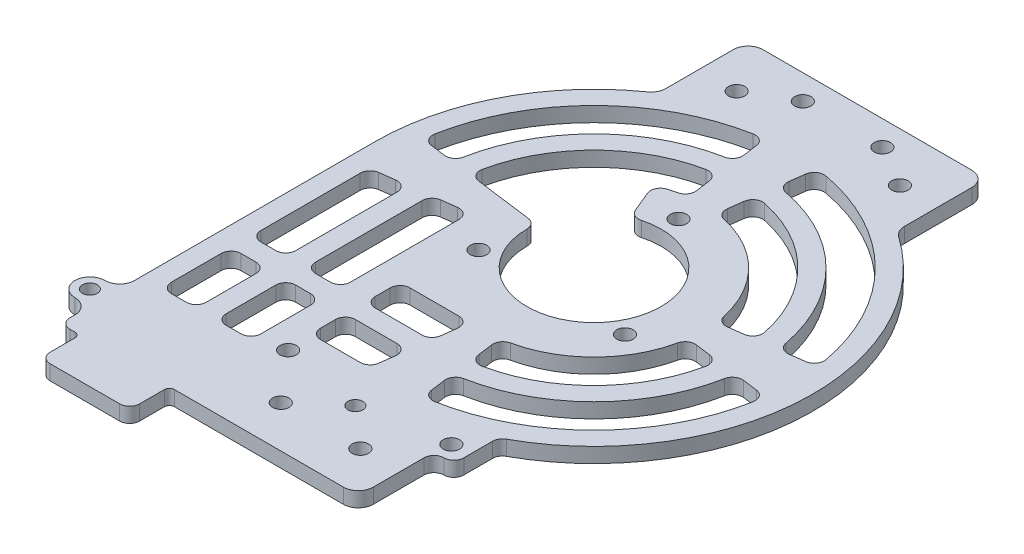
SolidWorks part; units mm, degrees
material "Thornel Mat VMA"
ref_plane "前视基准面" through (0, 0, 0) normal (0, 0, 1) x (1, 0, 0)
ref_plane "上视基准面" through (0, 0, 0) normal (0, 1, 0) x (1, 0, 0)
ref_plane "右视基准面" through (0, 0, 0) normal (1, 0, 0) x (0, 0, -1)
other "Configuration Table"
sketch "草图1" plane through (0, 0, 0) normal (0, 1, 0) x (1, 0, 0)
  line L0 (-44, 0) -> (-44, -52)
  line L1 (-44, -52) -> (16, -52)
  line L2 (-21.8118, 2.8716) -> (-13.3845, 1.7621)
  line L3 (-2.8716, 21.8118) -> (-3.7853, 28.7519)
  line L4 (2.8716, 21.8118) -> (3.7853, 28.7519)
  line L5 (0, 0) -> (0, 69.078) construction
  line L6 (21.8118, -2.8716) -> (28.7519, -3.7853)
  line L7 (21.8118, 2.8716) -> (28.7519, 3.7853)
  line L8 (-2.8716, -21.8118) -> (-3.7853, -28.7519)
  line L9 (2.8716, -21.8118) -> (3.7853, -28.7519)
  line L10 (-21.8118, 2.8716) -> (-28.7519, 3.7853)
  line L11 (-21.8118, -2.8716) -> (-28.7519, -3.7853)
  line L12 (32.7177, 4.3074) -> (39.6578, 5.221)
  line L13 (32.7177, -4.3074) -> (39.6578, -5.221)
  line L14 (-4.3074, 32.7177) -> (-5.221, 39.6578)
  line L15 (4.3074, 32.7177) -> (5.221, 39.6578)
  line L16 (-32.7177, 4.3074) -> (-39.6578, 5.221)
  line L17 (-32.7177, -4.3074) -> (-39.6578, -5.221)
  line L18 (-4.3074, -32.7177) -> (-5.221, -39.6578)
  line L19 (4.3074, -32.7177) -> (5.221, -39.6578)
  line L20 (21.8118, 2.8716) -> (13.3845, 1.7621)
  line L21 (-5.1662, 12.4724) -> (-8.419, 20.3253)
  line L22 (5.1662, 12.4724) -> (8.419, 20.3253)
  arc A0 (44, 0) -> (-44, 0) centre (0, 0) ccw
  circle A1 centre (0, 0) radius 31 construction
  circle A2 centre (0, 0) radius 17 construction
  circle A3 centre (0, 17) radius 1.65
  circle A4 centre (14.7224, -8.5) radius 1.65
  circle A5 centre (-14.7224, -8.5) radius 1.65
  circle A6 centre (0, 0) radius 13.5
  arc A7 (21.8118, 2.8716) -> (2.8716, 21.8118) centre (0, 0) ccw
  arc A8 (28.7519, 3.7853) -> (3.7853, 28.7519) centre (0, 0) ccw
  arc A9 (32.7177, 4.3074) -> (4.3074, 32.7177) centre (0, 0) ccw
  arc A10 (39.6578, 5.221) -> (5.221, 39.6578) centre (0, 0) ccw
  arc A11 (-2.8716, 21.8118) -> (-21.8118, 2.8716) centre (0, 0) ccw
  arc A12 (-3.7853, 28.7519) -> (-28.7519, 3.7853) centre (0, 0) ccw
  arc A13 (-4.3074, 32.7177) -> (-32.7177, 4.3074) centre (0, 0) ccw
  arc A14 (-5.221, 39.6578) -> (-39.6578, 5.221) centre (0, 0) ccw
  arc A15 (-32.7177, -4.3074) -> (-4.3074, -32.7177) centre (0, 0) ccw
  arc A16 (-28.7519, -3.7853) -> (-3.7853, -28.7519) centre (0, 0) ccw
  arc A17 (-39.6578, -5.221) -> (-5.221, -39.6578) centre (0, 0) ccw
  arc A18 (3.7853, -28.7519) -> (28.7519, -3.7853) centre (0, 0) ccw
  arc A19 (4.3074, -32.7177) -> (32.7177, -4.3074) centre (0, 0) ccw
  arc A20 (5.221, -39.6578) -> (39.6578, -5.221) centre (0, 0) ccw
  arc A21 (2.8716, -21.8118) -> (21.8118, -2.8716) centre (0, 0) ccw
  arc A22 (-21.8118, -2.8716) -> (-2.8716, -21.8118) centre (0, 0) ccw
  arc A24 (44, 0) -> (16, -52) centre (-18.2857, 0) cw
  point P17 (0, 0)
  point P40 (0, 0)
  dimension "D1" = 88
  dimension "D2" = 62
  dimension "D3" = 34
  dimension "D4" = 3.3
  dimension "D8" = 27
  dimension "D9" = 44
  dimension "D10" = 58
  dimension "D11" = 66
  dimension "D12" = 80
  dimension "D5" = 52
  dimension "D6" = 60
  dimension "D13" = 15
  dimension "D15" = 22.5
  dimension "D16" = 22.5
  dimension "D7" = 3
  dimension "D14" = 4
extrude "凸台-拉伸1" add sketch "草图1" along normal blind 3 contours A0 A20 L19 A19 L13 A17 L17 A15 L18 A14 L14 A13 L16 A12 L3 A11 L10 A10 L12 A9 L15 A8 L7 A7 L4 A6 A5 A4 A3 L9 A21 L6 A18 L11 A22 L8 A16 | A0 L0 L1 | L20 A7 L22 A6 | L18 A17 L17 A15 | L8 A16 L11 A22 region at (0, 0, -42.6977) region at (13.7043, 0, -10.5157)
sketch "草图2" plane through (0, 3, 0) normal (0, 1, 0) x (1, 0, 0)
  line L0 (-31, 0) -> (-31, -68.0994) construction
  line L1 (-4.0812, -31) -> (-59.0383, -31) construction
  line L2 (-29, -3.8179) -> (-29, -29)
  line L3 (-33, -4.3445) -> (-33, -29)
  line L4 (-40, -5.2661) -> (-40, -29)
  line L5 (-22, -2.8964) -> (-22, -29)
  line L6 (-44, 0) -> (-44, -52) construction
  line L7 (-3.8179, -29) -> (-17, -29)
  line L8 (-4.3445, -33) -> (-17, -33)
  line L9 (-5.2661, -40) -> (-17, -40)
  line L10 (-2.8964, -22) -> (-17, -22)
  line L11 (-22, -2.8964) -> (-29, -3.8179)
  line L12 (-40, -47) -> (-33, -47)
  line L13 (-29, -47) -> (-22, -47)
  line L14 (-44, -52) -> (16, -52) construction
  line L15 (-33, -4.3445) -> (-40, -5.2661)
  line L16 (-17, -22) -> (-17, -29)
  line L19 (-17, -33) -> (-17, -40)
  line L20 (-2.8964, -22) -> (-3.8179, -29)
  line L21 (-4.3445, -33) -> (-5.2661, -40)
  line L22 (-22, -29) -> (-29, -29)
  line L23 (-22, -33) -> (-29, -33)
  line L24 (-40, -33) -> (-40, -47)
  line L25 (-33, -33) -> (-33, -47)
  line L26 (-33, -29) -> (-40, -29)
  line L27 (-33, -33) -> (-40, -33)
  line L28 (-29, -33) -> (-29, -47)
  line L29 (-22, -33) -> (-22, -47)
  dimension "D1" = 31
  dimension "D2" = 31
  dimension "D3" = 2
  dimension "D4" = 2
  dimension "D5" = 4
  dimension "D6" = 22
  dimension "D7" = 97.5
  dimension "D8" = 5
  dimension "D9" = 2
  dimension "D10" = 2
  dimension "D11" = 97.5
  dimension "D12" = 9
  dimension "D13" = 9
  dimension "D14" = 5
extrude "切除-拉伸1" cut sketch "草图2" against normal blind 5
fillet "圆角1" radius 2 50 edges at (5.221, 1.5, 39.6578) (4.3074, 1.5, 32.7177) (32.7177, 1.5, 4.3074) (39.6578, 1.5, 5.221) (-5.221, 1.5, -39.6578) (-4.3074, 1.5, -32.7177) (-32.7177, 1.5, -4.3074) (-39.6578, 1.5, -5.221) (-3.7853, 1.5, -28.7519) (-2.8716, 1.5, -21.8118) (-28.7519, 1.5, -3.7853) (39.6578, 1.5, -5.221) (32.7177, 1.5, -4.3074) (4.3074, 1.5, -32.7177) (5.221, 1.5, -39.6578) (28.7519, 1.5, -3.7853) (21.8118, 1.5, -2.8716) (2.8716, 1.5, -21.8118) (3.7853, 1.5, -28.7519) (2.8716, 1.5, 21.8118) (21.8118, 1.5, 2.8716) (28.7519, 1.5, 3.7853) (3.7853, 1.5, 28.7519) (-17, 1.5, 40) (-17, 1.5, 33) (-4.3445, 1.5, 33) (-5.2661, 1.5, 40) (-29, 1.5, 3.8179) (-22, 1.5, 2.8964) (-2.8964, 1.5, 22) (-3.8179, 1.5, 29) (-17, 1.5, 29) (-17, 1.5, 22) (-33, 1.5, 4.3445) (-40, 1.5, 5.2661) (-22, 1.5, 29) (-29, 1.5, 29) (-40, 1.5, 47) (-40, 1.5, 33) (-33, 1.5, 33) (-33, 1.5, 47) (-22, 1.5, 47) (-29, 1.5, 47) (-29, 1.5, 33) (-33, 1.5, 29) (-40, 1.5, 29) (-22, 1.5, 33) (-5.1662, 1.5, -12.4724) (-8.419, 1.5, -20.3253) (-13.3845, 1.5, -1.7621)
sketch "草图5" plane through (0, 3, 0) normal (0, 1, 0) x (1, 0, 0)
  circle A0 centre (-48, 0) radius 1.5
  circle A1 centre (-48, 0) radius 5
  circle A3 centre (-48, -31) radius 1.5
  circle A4 centre (-48, -31) radius 5
  dimension "D1" = 3
  dimension "D3" = 10
  dimension "D4" = 31
  dimension "D2" = 48
extrude "凸台-拉伸2" [suppressed] add sketch "草图5" against normal blind 3
fillet "圆角2" [suppressed] radius 6
sketch "草图4" plane through (0, 3, 0) normal (0, 1, 0) x (1, 0, 0)
  circle A0 centre (0, -48) radius 1.5
  dimension "D1" = 3
  dimension "D2" = 48
extrude "切除-拉伸2" cut sketch "草图4" against normal blind 3
sketch "草图6" plane through (0, 3, 0) normal (0, 1, 0) x (1, 0, 0)
  line L0 (-24, 36.8782) -> (-24, 55)
  line L1 (-24, 55) -> (24, 55)
  line L2 (24, 55) -> (24, 36.8782)
  line L3 (0, 0) -> (0, 61.0377) construction
  line L4 (0, 0) -> (64.4608, 0) construction
  line L5 (16, -52) -> (16, -65)
  line L6 (16, -65) -> (-16, -65)
  line L7 (-16, -65) -> (-16, -52)
  line L8 (-44, -52) -> (16, -52) construction
  line L9 (-16, -52) -> (16, -52)
  line L10 (16.417, 45.1052) -> (0, 0) construction
  arc A0 (44, 0) -> (-44, 0) centre (0, 0) ccw construction
  arc A1 (24, 36.8782) -> (-24, 36.8782) centre (0, 0) ccw
  circle A2 centre (-8, 50) radius 1.65
  circle A3 centre (8, 50) radius 1.65
  circle A4 centre (-8, -55) radius 1.65
  circle A6 centre (8, -55) radius 1.65
  circle A7 centre (16.417, 45.1052) radius 1.65
  circle A8 centre (-16.417, 45.1052) radius 1.65
  dimension "D3" = 3.3
  dimension "D6" = 3.3
  dimension "D10" = 24
  dimension "D1" = 55
  dimension "D2" = 65
  dimension "D4" = 5
  dimension "D5" = 8
  dimension "D7" = 10
  dimension "D8" = 48
  dimension "D9" = 20
extrude "凸台-拉伸3" add sketch "草图6" against normal blind 3
sketch "草图7" plane through (0, 3, 0) normal (0, 1, 0) x (1, 0, 0)
  line L0 (0, 0) -> (63.65, 0) construction
  circle A0 centre (16.417, 45.1052) radius 1.65 construction
  circle A1 centre (-16.417, 45.1052) radius 1.65 construction
  circle A2 centre (16.417, 45.1052) radius 1.65 construction
  circle A3 centre (-16.417, 45.1052) radius 1.65 construction
  circle A4 centre (-16.417, -45.1052) radius 1.65
  circle A5 centre (16.417, -45.1052) radius 1.65
extrude "切除-拉伸3" cut sketch "草图7" against normal through all
sketch "草图8" plane through (0, 3, 0) normal (0, 1, 0) x (1, 0, 0)
  line L0 (16, -52) -> (16, -48.1918)
  line L1 (16, -48.1918) -> (20, -48.1918)
  line L2 (20, -48.1918) -> (20, -39.1918)
  line L3 (-44, 0) -> (-44, -52) construction
  line L12 (24, 36.8782) -> (24, 55)
  line L13 (24, 55) -> (-24, 55)
  line L14 (-24, 55) -> (-24, 36.8782)
  line L15 (-44, 0) -> (-44, -52)
  line L16 (-44, -52) -> (-16, -52)
  line L17 (-16, -52) -> (-16, -65)
  line L18 (-16, -65) -> (16, -65)
  line L19 (16, -65) -> (16, -52)
  line L20 (24, 36.8782) -> (24, 55)
  line L21 (24, 55) -> (-24, 55)
  line L22 (-24, 55) -> (-24, 36.8782)
  line L23 (-44, 0) -> (-44, -52)
  line L24 (-44, -52) -> (-16, -52)
  line L25 (-16, -52) -> (-16, -65)
  line L26 (-16, -65) -> (16, -65)
  line L27 (16, -65) -> (16, -52)
  circle A0 centre (0, 0) radius 44
  arc A15 (-24, 36.8782) -> (-44, 0) centre (0, 0) ccw
  arc A20 (16, -52) -> (44, 0) centre (-18.2857, 0) ccw
  arc A21 (44, 0) -> (24, 36.8782) centre (0, 0) ccw
  arc A26 (-24, 36.8782) -> (-44, 0) centre (0, 0) ccw
  arc A31 (16, -52) -> (44, 0) centre (-18.2857, 0) ccw
  arc A32 (44, 0) -> (24, 36.8782) centre (0, 0) ccw
  dimension "D1" = 88
  dimension "D2" = 9
  dimension "D3" = 64
  dimension "D4" = 0
extrude "切除-拉伸4" cut sketch "草图8" against normal blind 10 contours L0 A31 A0 L2 L1 region at (28.674, 3, 35.8569)
fillet "圆角4" radius 2 3 edges at (20, 1.5, 39.1918) (16, 1.5, 48.1918) (20, 1.5, 48.1918)
sketch "草图9" plane through (0, 3, 0) normal (0, 1, 0) x (1, 0, 0)
  line L0 (-16, -52) -> (-16, -65) construction
  line L1 (-44, -52) -> (-16, -52)
  line L2 (-44, -52) -> (-44, -63.4)
  line L3 (-44, -63.4) -> (-16, -63.4)
  line L4 (-16, -52) -> (-16, -63.4)
  dimension "D1" = 11.4
extrude "凸台-拉伸4" add sketch "草图9" against normal blind 3
sketch "草图10" plane through (0, 3, 0) normal (0, 1, 0) x (1, 0, 0)
  line L1 (16, -65) -> (-16, -65)
  line L2 (16, -65) -> (16, -63.4)
  line L3 (16, -63.4) -> (-16, -63.4)
  line L4 (-16, -65) -> (-16, -63.4)
extrude "切除-拉伸5" cut sketch "草图10" against normal blind 4
sketch "草图11" plane through (0, 3, 0) normal (0, 1, 0) x (1, 0, 0)
  line L0 (-44, 0) -> (-44, -63.4) construction
  line L1 (-44, -63.4) -> (16, -63.4) construction
  line L2 (-50, -57.4) -> (-44, -57.4)
  line L3 (-50, -57.4) -> (-50, -51.4)
  line L4 (-50, -51.4) -> (-44, -51.4)
  line L5 (-44, -57.4) -> (-44, -51.4)
  line L6 (-50, -57.4) -> (-44, -51.4) construction
  line L7 (-50, -51.4) -> (-44, -57.4) construction
  circle A0 centre (-47, -54.4) radius 1.5
  dimension "D1" = 3
  dimension "D2" = 3
  dimension "D3" = 9
extrude "凸台-拉伸5" add sketch "草图11" against normal blind 3
sketch "草图12" plane through (0, 3, 0) normal (0, 1, 0) x (1, 0, 0)
  line L0 (-40, -63.4) -> (-40, -71.4)
  line L1 (-44, -63.4) -> (16, -63.4) construction
  line L2 (-40, -71.4) -> (-22, -71.4)
  line L3 (-22, -71.4) -> (-22, -63.4)
  line L4 (-44, 0) -> (-44, -51.4) construction
  line L5 (-44, -63.4) -> (16, -63.4) construction
  line L6 (-40, -63.4) -> (-22, -63.4)
  dimension "D1" = 4
  dimension "D2" = 18
  dimension "D3" = 8
extrude "凸台-拉伸6" add sketch "草图12" against normal up to surface (3 mm away) up to face at (-8, 0, 56.65)
fillet "圆角5" radius 3 9 edges at (24, 1.5, -36.8782) (24, 1.5, -55) (-24, 1.5, -55) (-24, 1.5, -36.8782) (-44, 1.5, 51.4) (-50, 1.5, 57.4) (-44, 1.5, 57.4) (16, 1.5, 63.4) (-50, 1.5, 51.4)
fillet "圆角6" radius 2 3 edges at (-22, 1.5, 71.4) (-40, 1.5, 71.4) (-44, 1.5, 63.4)
fillet "圆角7" radius 1 2 edges at (-22, 1.5, 63.4) (-40, 1.5, 63.4)
